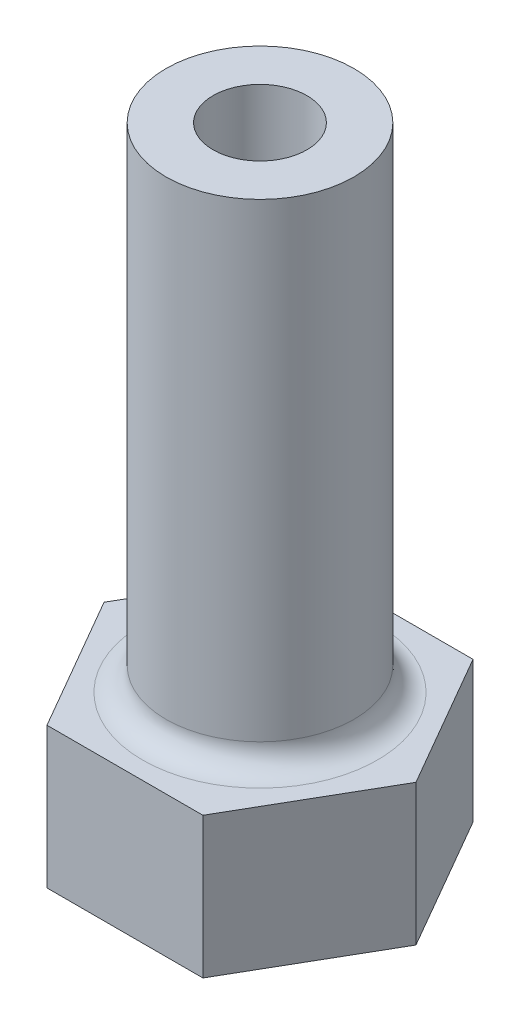
SolidWorks part; units mm, degrees
ref_plane "前视基准面" through (0, 0, 0) normal (0, 0, 1) x (1, 0, 0)
ref_plane "上视基准面" through (0, 0, 0) normal (0, 1, 0) x (1, 0, 0)
ref_plane "右视基准面" through (0, 0, 0) normal (1, 0, 0) x (0, 0, -1)
other "Configuration Table"
sketch "草图1" plane through (0, 0, 0) normal (0, 1, 0) x (1, 0, 0)
  line L1 (6.6395, 0) -> (3.3198, 5.75)
  line L2 (3.3198, 5.75) -> (-3.3198, 5.75)
  line L3 (-3.3198, 5.75) -> (-6.6395, 0)
  line L4 (-6.6395, 0) -> (-3.3198, -5.75)
  line L5 (-3.3198, -5.75) -> (3.3198, -5.75)
  line L6 (3.3198, -5.75) -> (6.6395, 0)
  circle A0 centre (0, 0) radius 4
  circle A1 centre (0, 0) radius 5.75 construction
  dimension "D1" = 8
  dimension "D2" = 11.5
extrude "凸台-拉伸2" add sketch "草图1" along normal blind 27 contours A0
extrude "凸台-拉伸3" add sketch "草图1<5>" along normal blind 6
sketch "草图1<5>" plane through (0, 0, 0) normal (0, 1, 0) x (1, 0, 0) same geometry as "草图1"
fillet "圆角1" radius 1 1 edges at (0, 6, 4)
sketch "草图2" plane through (0, 0, 0) normal (0, 1, 0) x (1, 0, 0)
  circle A0 centre (0, 0) radius 2
  dimension "D1" = 4
extrude "切除-拉伸1" cut sketch "草图2" against normal through all both and the other way through all
